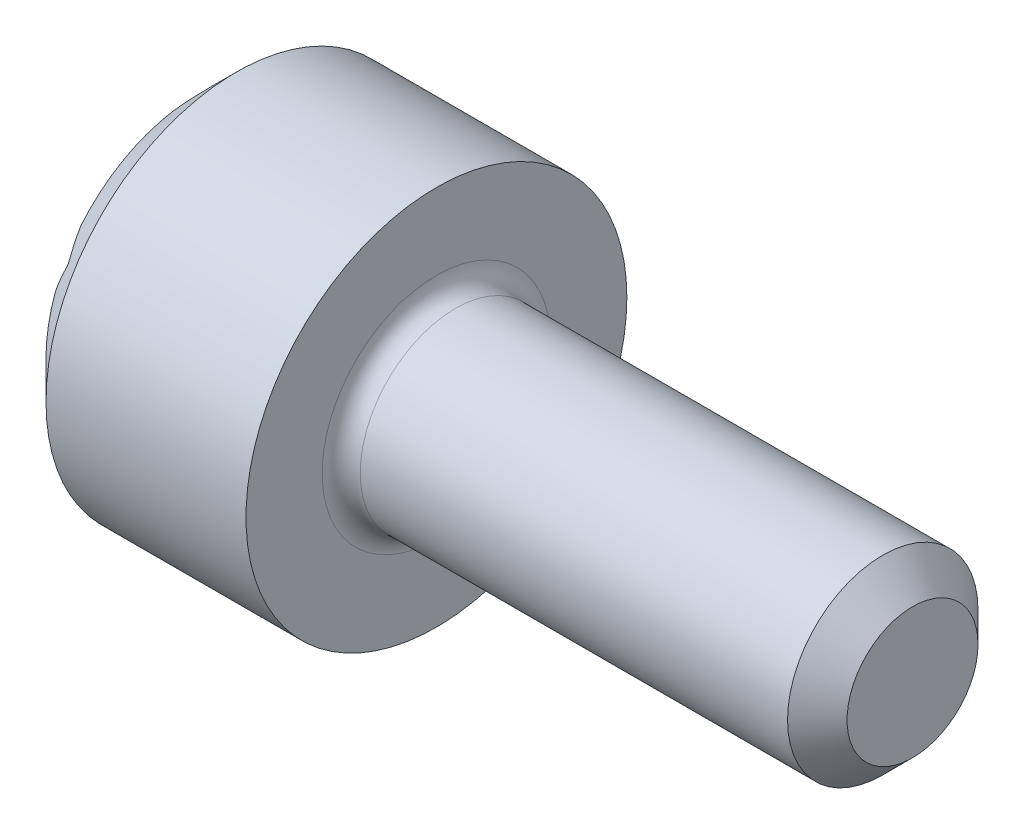
SolidWorks part; units mm, degrees
material "NA"
ref_plane "Front Plane" through (0, 0, 0) normal (0, 0, 1) x (1, 0, 0)
ref_plane "Top Plane" through (0, 0, 0) normal (0, 1, 0) x (1, 0, 0)
ref_plane "Right Plane" through (0, 0, 0) normal (1, 0, 0) x (0, 0, -1)
sketch "Sketch1" plane through (0, 0, 0) normal (0, 1, 0) x (1, 0, 0)
  line L0 (0, 0) -> (0, 4)
  line L1 (0, 4) -> (5, 4)
  line L2 (5, 4) -> (5, 2)
  line L3 (5, 2) -> (15, 2)
  line L4 (15, 2) -> (15, 0)
  line L5 (15, 0) -> (0, 0)
  dimension "16" = 5
  dimension "D2" = 4
  dimension "D3" = 2
  dimension "20" = 10
revolve "Revolve1" add sketch "Sketch1" angle 360 about L5
chamfer "Chamfer1" distance 0.625 angle 45 1 edges at (15, 0, -2)
sketch "Sketch3" plane through (0, 0, 0) normal (0, 1, 0) x (1, 0, 0)
  line L0 (0, 0) -> (5.7321, 0)
  line L1 (0, 4) -> (0, -4) construction
  line L2 (5.7321, 0) -> (4, 3)
  line L3 (4, 3) -> (0, 3)
  line L4 (0, 3) -> (0, 0)
  dimension "5" = 3
  dimension "D2" = 4
  dimension "D3" = 60
revolve "Cut-Revolve1" cut sketch "Sketch3" angle 360 about L0
sketch "Sketch2" plane through (0, 0, 0) normal (-1, 0, 0) x (0, 0, 1)
  line L0 (0, 0) -> (0, 3.4641) construction
  line L1 (0, 3.4641) -> (-3, 1.7321)
  line L2 (-3, 1.7321) -> (-3, -1.7321)
  line L3 (-3, -1.7321) -> (0, -3.4641)
  line L4 (0, -3.4641) -> (3, -1.7321)
  line L5 (3, -1.7321) -> (3, 1.7321)
  line L6 (3, 1.7321) -> (0, 3.4641)
  circle A0 centre (0, 0) radius 3 construction
  dimension "4" = 6
extrude "Cut-Extrude1" cut sketch "Sketch2" against normal blind 4 contours L4 L5 L6 L1 L2 L3
chamfer "Chamfer2" distance 0.8 angle 45 1 edges at (0, 0, -4)
fillet "Fillet1" radius 0.4 1 edges at (5, 0, -2)
ref_plane "Plane1" through (16.6, 0, 0) normal (1, 0, 0) x (0, 0, -1)
sketch "Sketch5" plane through (16.6, 0, 0) normal (1, 0, 0) x (0, 0, -1)
  circle A0 centre (0, 0) radius 4
  dimension "D1" = 8
curve "Helix/Spiral1" pitch 1.25 height 30 turns 24
sketch "Sketch6" plane through (0, 0, 0) normal (0, 0, 1) x (1, 0, 0)
  line L0 (15.9873, 4.1353) -> (16.6, 3.0524) construction
  line L1 (16.6, 3.0524) -> (17.2127, 4.1353) construction
  line L2 (17.2127, 4.1353) -> (15.9873, 4.1353) construction
  line L3 (16.6, 4.1353) -> (16.6, 3.0524) construction
  line L4 (16.0639, 4) -> (17.1361, 4)
  line L5 (16.0639, 4) -> (16.4469, 3.323)
  line L6 (16.7531, 3.323) -> (17.1361, 4)
  line L7 (16.7531, 3.323) -> (16.4469, 3.323)
  point P6 (16.6, 4)
  dimension "D1" = 59
  dimension "D2" = 0.677
  dimension "D3" = 0.1353
  dimension "D4" = 0.2706
sweep "Cut-Sweep2" [suppressed] cut profiles "Sketch6" path "Helix/Spiral1"
